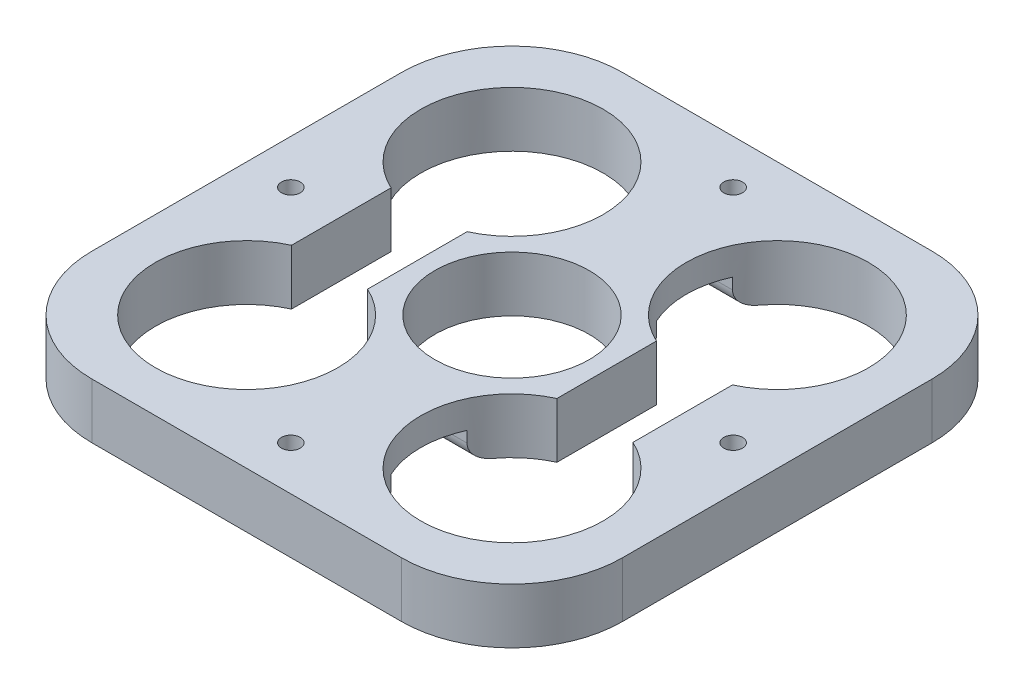
SolidWorks part; units mm, degrees
material "PET"
ref_plane "Front Plane" through (0, 0, 0) normal (0, 0, 1) x (1, 0, 0)
ref_plane "Top Plane" through (0, 0, 0) normal (0, 1, 0) x (1, 0, 0)
ref_plane "Right Plane" through (0, 0, 0) normal (1, 0, 0) x (0, 0, -1)
sketch "Sketch1" plane through (0, 0, 0) normal (0, 1, 0) x (1, 0, 0)
  line L0 (0, 0) -> (-48, 0) construction
  line L1 (-48, 48) -> (48, 48)
  line L2 (-48, 48) -> (-48, -48)
  line L3 (-48, -48) -> (48, -48)
  line L4 (48, 48) -> (48, -48)
  line L7 (0, 0) -> (0, 48) construction
  circle A0 centre (-24, 24) radius 16.5
  circle A1 centre (24, 24) radius 16.5
  circle A2 centre (24, -24) radius 16.5
  circle A3 centre (-24, -24) radius 16.5
  circle A4 centre (0, 0) radius 13.97
  point P4 (48, 0)
  point P6 (0, 48)
  point P8 (0, 24)
  point P9 (-24, 0)
  dimension "D1" = 33
  dimension "D3" = 27.94
  dimension "D2" = 48
  dimension "D4" = 48
extrude "Boss-Extrude1" add sketch "Sketch1" along normal blind 10
fillet "Fillet1" radius 20 4 edges at (-48, 5, -48) (48, 5, -48) (48, 5, 48) (-48, 5, 48)
sketch "Sketch4" plane through (0, 0, 0) normal (0, -1, 0) x (1, 0, 0)
  line L0 (0, 40) -> (0, -40) construction
  line L1 (-40, 0) -> (40, 0) construction
  circle A0 centre (0, 0) radius 40 construction
  dimension "D1" = 80
hole_wizard "M3 Clearance Hole1" positions "3DSketch2" profile "Sketch6" hole size "M3" standard "ANSI Metric" end condition through all
sketch3d "3DSketch2"
  point P0 (-40, 0, 0)
  point P3 (0, 0, 40)
  point P6 (40, 0, 0)
  point P9 (0, 0, -40)
sketch "Sketch6" plane through (-40, 0, 0) normal (1, 0, 0) x (0, 0, -1)
  line L0 (0, 0) -> (0, 10)
  line L1 (0, 10) -> (1.7, 10)
  line L2 (1.7, 10) -> (1.7, 0.025)
  line L3 (1.7, 0.025) -> (1.725, 0)
  line L5 (1.725, 0) -> (0, 0)
  line L6 (-1.7, 0.025) -> (-1.725, 0) construction
  line L11 (0, -6.35) -> (0, 107.95) construction
  dimension "Thru Hole Dia." = 3.4
  dimension "Thru Hole Depth" = 10
  dimension "Near C'Sink Dia." = 3.45
  dimension "Near C'Sink Angle" = 90
sketch "Sketch7" plane through (0, 0, 0) normal (0, -1, 0) x (1, 0, 0)
  line L0 (30.8739, 9) -> (17.1261, 9)
  line L1 (-9, 30.8739) -> (9, 30.8739)
  line L2 (-9, 30.8739) -> (-9, 17.1261)
  line L3 (-9, 17.1261) -> (9, 17.1261)
  line L4 (9, 30.8739) -> (9, 17.1261)
  line L5 (30.8739, 9) -> (30.8739, -9)
  line L6 (30.8739, -9) -> (17.1261, -9)
  line L7 (17.1261, 9) -> (17.1261, -9)
  line L8 (9, -30.8739) -> (9, -17.1261)
  line L9 (9, -30.8739) -> (-9, -30.8739)
  line L10 (-9, -30.8739) -> (-9, -17.1261)
  line L11 (9, -17.1261) -> (-9, -17.1261)
  line L12 (-30.8739, -9) -> (-17.1261, -9)
  line L13 (-30.8739, -9) -> (-30.8739, 9)
  line L14 (-30.8739, 9) -> (-17.1261, 9)
  line L15 (-17.1261, -9) -> (-17.1261, 9)
  circle A0 centre (-24, 24) radius 16.5 construction
  circle A1 centre (24, 24) radius 16.5 construction
  point P23 (0, 0)
  circle M17 centre (-24, -24) radius 16.5
  circle M18 centre (24, -24) radius 16.5
  circle M19 centre (24, 24) radius 16.5
  circle M20 centre (-24, 24) radius 16.5
  dimension "D1" = 18
  dimension "D2" = 4
extrude "Cut-Extrude1" cut sketch "Sketch7" against normal blind 5 contours L3 L1 M20 M19 | L11 L9 M18 M17 region at (0, 0, 24) region at (0, 0, -24)
fillet "Fillet2" radius 3 4 edges at (0, 0, -30.8739) (0, 0, -17.1261) (0, 0, 30.8739) (0, 0, 17.1261)
extrude "Cut-Extrude2" cut sketch "Sketch7<3>" against normal through all contours L15 L13 M17 M20 | L7 L5 M19 M18 region at (24, 0, 0) region at (-24, 0, 0)
sketch "Sketch7<3>" plane through (0, 0, 0) normal (0, -1, 0) x (1, 0, 0) same geometry as "Sketch7"
